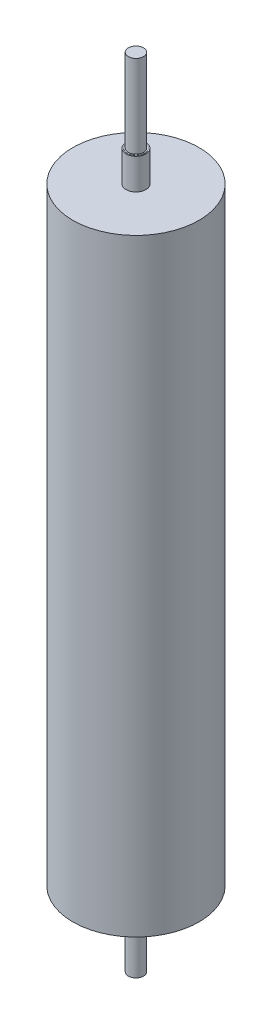
SolidWorks part; units mm, degrees
material "Stainless Steel (ferritic)"
ref_plane "Front Plane" through (0, 0, 0) normal (0, 0, 1) x (1, 0, 0)
ref_plane "Top Plane" through (0, 0, 0) normal (0, 1, 0) x (1, 0, 0)
ref_plane "Right Plane" through (0, 0, 0) normal (1, 0, 0) x (0, 0, -1)
sketch "Sketch1" plane through (0, 0, 0) normal (0, 1, 0) x (1, 0, 0)
  circle A0 centre (0, 0) radius 3.8495
  circle A1 centre (0, 0) radius 3.45
  circle A2 centre (0, 0) radius 2.95
  circle A3 centre (0, 0) radius 24.5
  dimension "D1" = 7.699
  dimension "D2" = 6.9
  dimension "D3" = 5.9
  dimension "D4" = 49
extrude "Boss-Extrude8" add sketch "Sketch1" along normal blind 236 contours A3
extrude "Boss-Extrude9" add sketch "Sketch1<9>" against normal blind 14 contours A0
sketch "Sketch1<9>" plane through (0, 0, 0) normal (0, 1, 0) x (1, 0, 0) same geometry as "Sketch1"
extrude "Boss-Extrude10" add sketch "Sketch1<10>" against normal blind 15 from surface contours A2 region at (0, 0, 0) starting at face at (0, -14, 3.8495)
sketch "Sketch1<10>" plane through (0, 0, 0) normal (0, 1, 0) x (1, 0, 0) same geometry as "Sketch1"
extrude "Boss-Extrude11" add sketch "Sketch1<11>" along normal blind 12 from surface contours A0 starting at face at (0, 236, 24.5)
sketch "Sketch1<11>" plane through (0, 0, 0) normal (0, 1, 0) x (1, 0, 0) same geometry as "Sketch1"
extrude "Boss-Extrude12" add sketch "Sketch1<12>" along normal blind 7.3 from surface contours A1 starting at face at (0, 248, 3.8495)
sketch "Sketch1<12>" plane through (0, 0, 0) normal (0, 1, 0) x (1, 0, 0) same geometry as "Sketch1"
extrude "Boss-Extrude13" add sketch "Sketch1<13>" along normal blind 25 from surface contours A2 starting at face at (0, 255.3, 3.45)
sketch "Sketch1<13>" plane through (0, 0, 0) normal (0, 1, 0) x (1, 0, 0) same geometry as "Sketch1"
sketch "Sketch2" plane through (0, 255.3, 0) normal (0, 1, 0) x (1, 0, 0)
  circle A0 centre (0, 0) radius 2.95
  circle A1 centre (0, 0) radius 3.45
extrude "Cut-Extrude1" cut sketch "Sketch2" against normal blind 7.23
